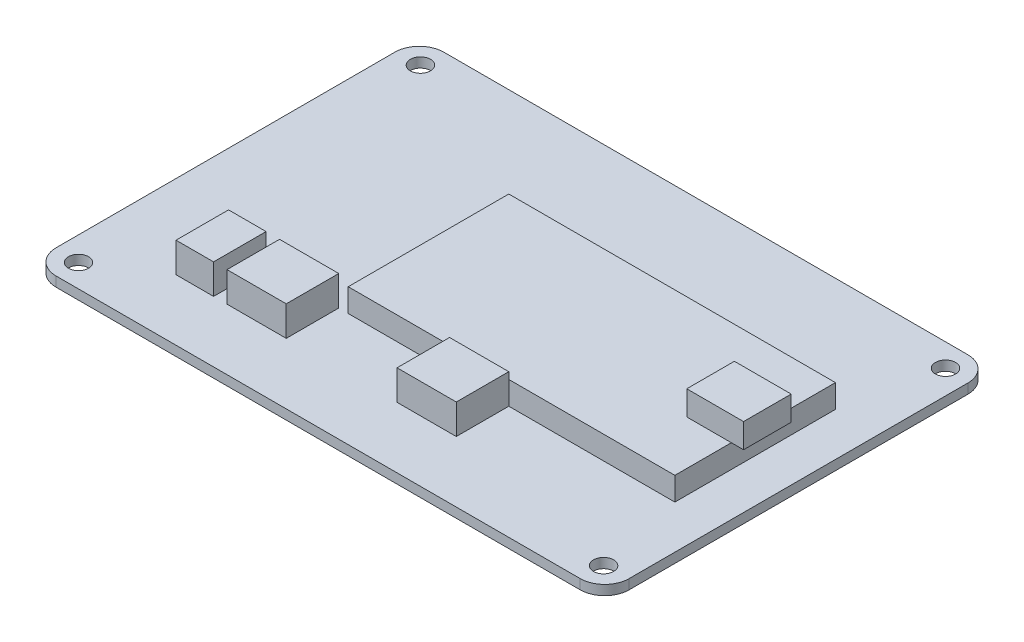
SolidWorks part; units mm, degrees
ref_plane "Front Plane" through (0, 0, 0) normal (0, 0, 1) x (1, 0, 0)
ref_plane "Top Plane" through (0, 0, 0) normal (0, 1, 0) x (1, 0, 0)
ref_plane "Right Plane" through (0, 0, 0) normal (1, 0, 0) x (0, 0, -1)
sketch "Sketch1" plane through (0, 0, 0) normal (0, 1, 0) x (1, 0, 0)
  line L0 (0, 31.75) -> (0, -31.75) construction
  line L1 (-46.925, 31.75) -> (46.925, 31.75)
  line L2 (-46.925, 31.75) -> (-46.925, -31.75)
  line L3 (-46.925, -31.75) -> (46.925, -31.75)
  line L4 (46.925, 31.75) -> (46.925, -31.75)
  line L5 (-46.925, 31.75) -> (46.925, -31.75) construction
  line L6 (-46.925, -31.75) -> (46.925, 31.75) construction
  line L7 (-46.925, 0) -> (46.925, 0) construction
  circle A0 centre (-43, 28) radius 1.65
  circle A1 centre (43, 28) radius 1.65
  circle A2 centre (43, -28) radius 1.65
  circle A3 centre (-43, -28) radius 1.65
  point P0 (0, 0)
  dimension "D3" = 3.3
  dimension "D4" = 86
  dimension "D1" = 63.5
  dimension "D2" = 93.85
  dimension "D5" = 56
extrude "Boss-Extrude1" add sketch "Sketch1" along normal blind 1.6
fillet "Fillet1" radius 4 4 edges at (-46.925, 0.8, -31.75) (46.925, 0.8, -31.75) (46.925, 0.8, 31.75) (-46.925, 0.8, 31.75)
sketch "Sketch2" plane through (0, 1.6, 0) normal (0, 1, 0) x (1, 0, 0)
  line L0 (-46.925, 0) -> (46.925, 0) construction
  line L1 (-46.925, 27.75) -> (-46.925, -27.75) construction
  line L2 (46.925, -27.75) -> (46.925, 27.75) construction
  line L4 (-13.675, 13.15) -> (39.825, 13.15)
  line L5 (-13.675, 13.15) -> (-13.675, -13.15)
  line L6 (-13.675, -13.15) -> (39.825, -13.15)
  line L7 (39.825, 13.15) -> (39.825, -13.15)
  line L8 (-13.675, 13.15) -> (39.825, -13.15) construction
  line L9 (-13.675, -13.15) -> (39.825, 13.15) construction
  point P6 (13.075, 0)
  dimension "D1" = 53.5
  dimension "D2" = 26.3
  dimension "D3" = 7.1
extrude "Boss-Extrude2" add sketch "Sketch2" along normal blind 3.8
sketch "Sketch3" plane through (0, 5.4, 0) normal (0, 1, 0) x (1, 0, 0)
  line L0 (-13.675, 0) -> (39.825, 0) construction
  line L1 (-13.675, 13.15) -> (-13.675, -13.15) construction
  line L2 (39.825, -13.15) -> (39.825, 13.15) construction
  line L4 (32.525, -3.9) -> (41.825, -3.9)
  line L5 (32.525, -3.9) -> (32.525, 3.9)
  line L6 (32.525, 3.9) -> (41.825, 3.9)
  line L7 (41.825, -3.9) -> (41.825, 3.9)
  line L8 (32.525, -3.9) -> (41.825, 3.9) construction
  line L9 (32.525, 3.9) -> (41.825, -3.9) construction
  point P6 (37.175, 0)
  dimension "D1" = 7.8
  dimension "D2" = 9.3
  dimension "D3" = 2
extrude "Boss-Extrude3" add sketch "Sketch3" along normal blind 4
sketch "Sketch4" plane through (0, 1.6, 0) normal (0, 1, 0) x (1, 0, 0)
  line L0 (-13.675, -13.15) -> (39.825, -13.15) construction
  line L1 (2.925, -13.15) -> (12.625, -13.15)
  line L2 (2.925, -13.15) -> (2.925, -21.75)
  line L3 (2.925, -21.75) -> (12.625, -21.75)
  line L4 (12.625, -13.15) -> (12.625, -21.75)
  line L5 (-13.675, 13.15) -> (-13.675, -13.15) construction
  line L7 (-15.225, -13.15) -> (-24.925, -13.15)
  line L8 (-15.225, -13.15) -> (-15.225, -21.75)
  line L9 (-15.225, -21.75) -> (-24.925, -21.75)
  line L10 (-24.925, -13.15) -> (-24.925, -21.75)
  line L11 (-27.125, -13.15) -> (-33.277, -13.15)
  line L12 (-27.125, -13.15) -> (-27.125, -21.75)
  line L13 (-27.125, -21.75) -> (-33.277, -21.75)
  line L14 (-33.277, -13.15) -> (-33.277, -21.75)
  dimension "D1" = 16.6
  dimension "D2" = 9.7
  dimension "D3" = 8.6
  dimension "D4" = 18.15
  dimension "D5" = 6.152
  dimension "D6" = 2.2
extrude "Boss-Extrude4" add sketch "Sketch4" along normal blind 4.9
